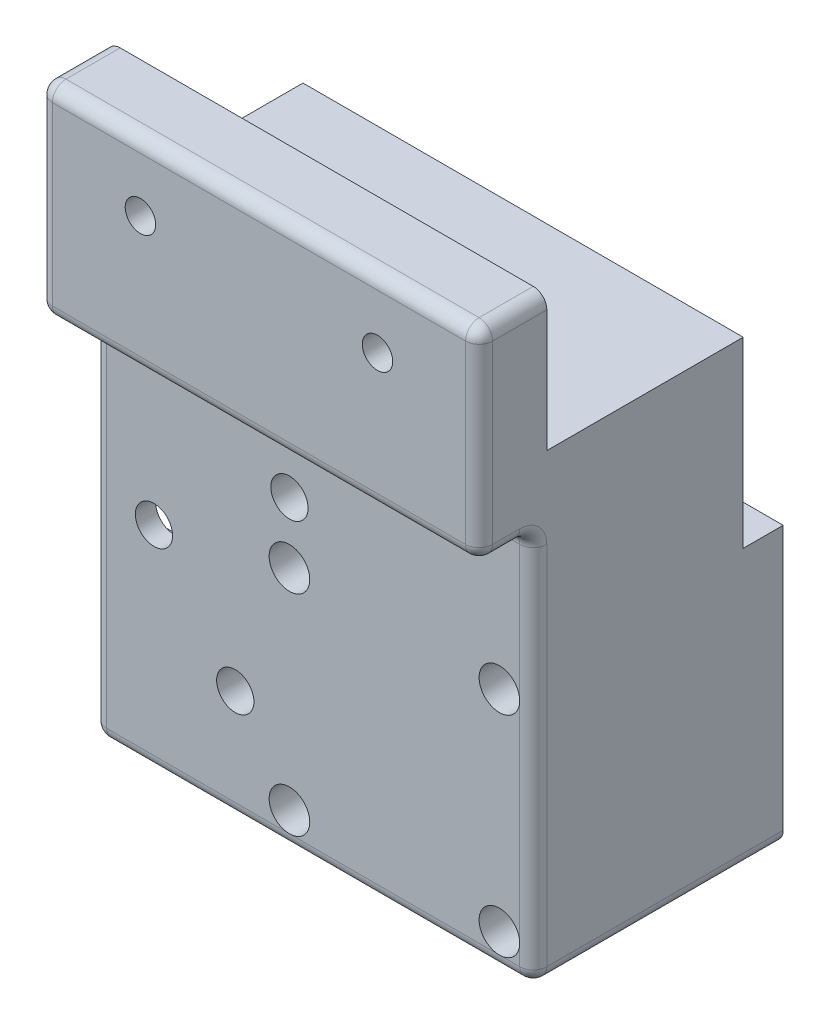
SolidWorks part; units mm, degrees
ref_plane "Front Plane" through (0, 0, 0) normal (0, 0, 1) x (1, 0, 0)
ref_plane "Top Plane" through (0, 0, 0) normal (0, 1, 0) x (1, 0, 0)
ref_plane "Right Plane" through (0, 0, 0) normal (1, 0, 0) x (0, 0, -1)
sketch "Sketch1" plane through (0, 0, 0) normal (0, 0, 1) x (1, 0, 0)
  line L1 (-44.5, 47.5) -> (20.5, 47.5)
  line L2 (-44.5, 47.5) -> (-44.5, -20.5)
  line L3 (-44.5, -20.5) -> (20.5, -20.5)
  line L4 (20.5, 47.5) -> (20.5, -20.5)
  circle A0 centre (0, 0) radius 12
  circle A1 centre (-15.5, 15.5) radius 1.75
  circle A2 centre (15.5, 15.5) radius 1.75
  circle A3 centre (15.5, -15.5) radius 1.75
  circle A4 centre (-15.5, -15.5) radius 1.75
  circle A6 centre (-15.5, 24.5) radius 2.75
  dimension "D1" = 24
  dimension "D2" = 31
  dimension "D3" = 31
  dimension "D4" = 31
  dimension "D5" = 31
  dimension "D6" = 15.5
  dimension "D7" = 15.5
  dimension "D8" = 0
  dimension "D9" = 3.5
  dimension "D10" = 3.5
  dimension "D11" = 3.5
  dimension "D12" = 3.5
  dimension "D13" = 23
  dimension "D14" = 29
  dimension "D16" = 5.5
  dimension "D21" = 47.5
  dimension "D22" = 44.5
  dimension "D19" = 65
  dimension "D20" = 68
extrude "Boss-Extrude1" add sketch "Sketch1" along normal blind 7
sketch "Sketch2" plane through (0, 0, 7) normal (0, 0, 1) x (1, 0, 0)
  line L0 (20.5, 47.5) -> (-44.5, 47.5) construction
  line L1 (-44.5, 47.5) -> (-44.5, -20.5) construction
  circle A0 centre (-15.5, 24.5) radius 2.75
  circle A6 centre (-35.5, 11) radius 2.75
  circle A8 centre (-23.5, -4.2471) radius 2.75
  circle A9 centre (-23.5, -4.2471) radius 7
  circle A10 centre (-15.5, 24.5) radius 7
  circle A11 centre (-35.5, 11) radius 4
  dimension "D1" = 14
  dimension "D2" = 5.5
  dimension "D3" = 5.5
  dimension "D4" = 8
  dimension "D6" = 14
  dimension "D5" = 23
  dimension "D8" = 29
  dimension "D9" = 36.5
  dimension "D10" = 9
  dimension "D11" = 51.7471
  dimension "D7" = 21
extrude "Boss-Extrude2" add sketch "Sketch2" along normal blind 2.65
sketch "Sketch3" plane through (20.5, 0, 0) normal (1, 0, 0) x (0, 0, -1)
  line L1 (-7, 47.5) -> (-29, 47.5)
  line L2 (-7, 47.5) -> (-7, 37.5)
  line L3 (-7, 37.5) -> (-29, 37.5)
  line L4 (-29, 47.5) -> (-29, 37.5)
  line L5 (-29, 37.5) -> (-39, 37.5)
  line L6 (-29, 37.5) -> (-29, 67.5)
  line L7 (-29, 67.5) -> (-39, 67.5)
  line L8 (-39, 37.5) -> (-39, 67.5)
  line M7 (-7, 47.5) -> (-7, -20.5)
  dimension "D1" = 22
  dimension "D2" = 10
  dimension "D3" = 20
  dimension "D4" = 10
extrude "Boss-Extrude3" add sketch "Sketch3" against normal through all contours L1 L4 L3 M7 | L8 L5 L4 L6 L7 region at (20.5, 42.5, 18) region at (20.5, 52.5, 34)
sketch "Sketch4" plane through (0, 0, 39) normal (0, 0, 1) x (1, 0, 0)
  line L0 (-44.5, 37.5) -> (20.5, 37.5) construction
  line L1 (-44.5, 67.5) -> (20.5, 67.5) construction
  line L2 (-44.5, 37.5) -> (-44.5, 67.5) construction
  line L3 (20.5, 37.5) -> (20.5, 67.5) construction
  circle A0 centre (-29.5, 57.5) radius 2.25
  circle A1 centre (5.5, 57.5) radius 2.25
  dimension "D1" = 4.5
  dimension "D2" = 20
  dimension "D3" = 10
  dimension "D4" = 15
  dimension "D5" = 10
  dimension "D6" = 15
  dimension "D7" = 4.5
extrude "Cut-Extrude1" cut sketch "Sketch4" against normal blind 10
sketch "Sketch5" plane through (0, 37.5, 0) normal (0, -1, 0) x (1, 0, 0)
  line L0 (-44.5, 7) -> (-44.5, 39) construction
  line L1 (-44.5, 39) -> (20.5, 39) construction
  line L2 (20.5, 7) -> (20.5, 39) construction
  circle A0 centre (-29.5, 19) radius 2.25
  circle A1 centre (5.5, 19) radius 2.25
  dimension "D1" = 15
  dimension "D2" = 20
  dimension "D3" = 20
  dimension "D4" = 15
  dimension "D5" = 4.5
  dimension "D6" = 4.5
extrude "Cut-Extrude2" cut sketch "Sketch5" against normal blind 10
sketch "Sketch7" plane through (0, 0, 0) normal (0, 0, -1) x (-1, 0, 0)
  line L1 (-20.5, -20.5) -> (20.5, -20.5)
  line L2 (-20.5, -20.5) -> (-20.5, 20.5)
  line L3 (-20.5, 20.5) -> (20.5, 20.5)
  line L4 (20.5, -20.5) -> (20.5, 20.5)
  circle A0 centre (0, 0) radius 12
  circle A1 centre (-15.5, 15.5) radius 1.75
  circle A2 centre (15.5, 15.5) radius 1.75
  circle A3 centre (15.5, -15.5) radius 1.75
  circle A4 centre (-15.5, -15.5) radius 1.75
  dimension "D2" = 5
  dimension "D3" = 5
  dimension "D4" = 5
  dimension "D1" = 5
extrude "Boss-Extrude5" add sketch "Sketch7" along normal blind 5.9
sketch "Sketch8" plane through (0, 0, 9.65) normal (0, 0, 1) x (1, 0, 0)
  circle A0 centre (-35.5, 11) radius 2.75
  circle A1 centre (-35.5, 11) radius 4
  dimension "D1" = 8
extrude "Boss-Extrude6" add sketch "Sketch8" along normal blind 7.95
sketch "Sketch10" plane through (0, 0, 7) normal (0, 0, 1) x (1, 0, 0)
  circle A0 centre (-35.5, 11) radius 2.75
  circle A1 centre (-23.5, -4.2471) radius 2.75
extrude "Cut-Extrude3" cut sketch "Sketch10" against normal blind 9.45
sketch "Sketch11" plane through (0, 0, 7) normal (0, 0, 1) x (1, 0, 0)
  line L1 (-44.5, 37.5) -> (20.5, 37.5)
  line L2 (-44.5, 37.5) -> (-44.5, -20.5)
  line L3 (-44.5, -20.5) -> (20.5, -20.5)
  line L4 (20.5, 37.5) -> (20.5, -20.5)
  circle A0 centre (-23.5, -4.2471) radius 10
  circle A1 centre (-15.5, 24.5) radius 10
  circle A2 centre (-15.5, 24.5) radius 2.75
  circle A3 centre (-23.5, -4.2471) radius 2.75
  circle A4 centre (0, 0) radius 7.25
  circle M1 centre (15.5, -15.5) radius 1.75
  circle M2 centre (-15.5, 15.5) radius 1.75
  circle M3 centre (0, 0) radius 12
  circle M4 centre (15.5, 15.5) radius 1.75
  circle M5 centre (-15.5, -15.5) radius 1.75
  circle M7 centre (-35.5, 11) radius 4
  line M9 (20.5, -20.5) -> (20.5, 37.5)
  line M10 (20.5, 37.5) -> (-44.5, 37.5)
  line M11 (-44.5, 37.5) -> (-44.5, -20.5)
  line M12 (-44.5, -20.5) -> (20.5, -20.5)
  dimension "D1" = 20
  dimension "D2" = 20
  dimension "D3" = 14.5
extrude "Boss-Extrude7" add sketch "Sketch11" along normal blind 10 contours A1 A0 M12 M9 M10 M11 M2 M4 M7 M5 M3 M1 | A4 M3 region at (-12.0095, 9.6819, 7) region at (-11.6606, 0, 7)
sketch "Sketch12" plane through (0, 0, 17) normal (0, 0, 1) x (1, 0, 0)
  line L1 (-11.6164, 26.7733) -> (3.0206, 1.7681)
  line L2 (-44.5, 37.5) -> (-44.5, -20.5) construction
  line L6 (-44.5, -20.5) -> (20.5, -20.5) construction
  line L7 (-44.5, 29) -> (-15.5, 29)
  line L8 (-44.5, 29) -> (-44.5, 32)
  line L9 (-44.5, 32) -> (-15.5, 32)
  line L13 (-9.0274, 28.2888) -> (5.6096, 3.2836)
  line L14 (-21.2843, 2.9181) -> (-1.034, -3.3438)
  line L17 (-22.1706, 0.052) -> (-1.9202, -6.2099)
  line L18 (-31, -4.2471) -> (-31, -20.5)
  line L20 (-31, -20.5) -> (-28, -20.5)
  line L21 (-28, -4.2471) -> (-28, -20.5)
  arc A5 (-21.2843, 2.9181) -> (-31, -4.2471) centre (-23.5, -4.2471) ccw
  arc A6 (-22.1706, 0.052) -> (-28, -4.2471) centre (-23.5, -4.2471) ccw
  arc A7 (-1.034, -3.3438) -> (3.0206, 1.7681) centre (0, 0) ccw
  arc A8 (-11.6164, 26.7733) -> (-15.5, 29) centre (-15.5, 24.5) ccw
  arc A9 (-9.0274, 28.2888) -> (-15.5, 32) centre (-15.5, 24.5) ccw
  arc A10 (-1.9202, -6.2099) -> (5.6096, 3.2836) centre (0, 0) ccw
  dimension "D4" = 3
  dimension "D5" = 3
  dimension "D6" = 3
  dimension "D7" = 3
extrude "Cut-Extrude4" cut sketch "Sketch12" against normal up to surface (7.35 mm away) up to face at (-16.5, -4.2471, 9.65)
sketch "Sketch13" plane through (0, 0, 17) normal (0, 0, 1) x (1, 0, 0)
  line L0 (-44.5, 29) -> (-44.5, -20.5) construction
  line L1 (-15.5, 34.5) -> (-44.5, 34.5)
  line L3 (-15.5, 14.5) -> (-44.5, 14.5)
  line L4 (-44.5, 34.5) -> (-44.5, 14.5)
  line L11 (-23.5, 5.7529) -> (-44.5, 5.7529)
  line L13 (-23.5, -14.2471) -> (-44.5, -14.2471)
  line L14 (-44.5, 5.7529) -> (-44.5, -14.2471)
  arc A0 (-15.5, 14.5) -> (-15.5, 34.5) centre (-15.5, 24.5) ccw
  circle A1 centre (-15.5, 24.5) radius 7
  circle A2 centre (-23.5, -4.2471) radius 7
  arc A4 (-23.5, -14.2471) -> (-23.5, 5.7529) centre (-23.5, -4.2471) ccw
extrude "Cut-Extrude5" cut sketch "Sketch13" against normal up to surface (10 mm away) up to face at (-15.5, 25.875, 7)
sketch "Sketch14" plane through (0, 0, 17) normal (0, 0, 1) x (1, 0, 0)
  circle A0 centre (15.5, 15.5) radius 3
  circle A1 centre (15.5, -15.5) radius 3
  circle A2 centre (-15.5, -15.5) radius 3
  circle A3 centre (-15.5, 15.5) radius 3
  dimension "D1" = 6
extrude "Cut-Extrude6" cut sketch "Sketch14" against normal blind 17
sketch "Sketch15" plane through (0, 0, 17) normal (0, 0, 1) x (1, 0, 0)
  line L0 (-44.5, 37.5) -> (20.5, 37.5)
  line L1 (20.5, 37.5) -> (20.5, -20.5)
  line L8 (-26.9872, 5.7529) -> (-23.5, 5.7529)
  line L9 (-26.1325, 14.5) -> (-18.3284, 14.5)
  line L10 (-15.5, 34.5) -> (-44.5, 34.5)
  line L11 (-44.5, 34.5) -> (-44.5, 37.5)
  line L12 (-14.9652, 0.9641) -> (-7.0998, -1.4681)
  line L13 (-4.9882, -5.2612) -> (-13.6389, -2.5862)
  line L14 (3.9873, 6.055) -> (-5.686, 22.5805)
  line L15 (-7.1051, 19.0663) -> (-0.1869, 7.2476)
  line L18 (-28, -20.5) -> (-28, -14.2471)
  line L19 (-28, -14.2471) -> (-23.5, -14.2471)
  line L21 (-44.5, -20.5) -> (-31, -20.5)
  line L22 (-44.5, -20.5) -> (-44.5, -14.2471)
  line L23 (-44.5, -14.2471) -> (-31, -14.2471)
  line L24 (-31, -20.5) -> (-31, -14.2471)
  line L25 (-28, -20.5) -> (20.5, -20.5)
  arc A0 (-12.5519, 14.9444) -> (-7.1051, 19.0663) centre (-15.5, 24.5) ccw
  arc A1 (-18.3284, 14.5) -> (-12.5519, 14.9444) centre (-15.5, 15.5) ccw
  arc A4 (-4.9882, -5.2612) -> (3.9873, 6.055) centre (0, 0) ccw
  circle A5 centre (15.5, 15.5) radius 3
  circle A6 centre (15.5, -15.5) radius 3
  arc A8 (-0.1869, 7.2476) -> (-7.0998, -1.4681) centre (0, 0) ccw
  arc A12 (-5.686, 22.5805) -> (-15.5, 34.5) centre (-15.5, 24.5) ccw
  circle A15 centre (-15.5, -15.5) radius 3
  arc A18 (-14.9652, 0.9641) -> (-23.5, 5.7529) centre (-23.5, -4.2471) ccw
  arc A19 (-26.9872, 5.7529) -> (-26.1325, 14.5) centre (-35.5, 11) ccw
  arc A20 (-23.5, -14.2471) -> (-13.6389, -2.5862) centre (-23.5, -4.2471) ccw
extrude "Boss-Extrude9" add sketch "Sketch15" along normal blind 3.5
sketch "Sketch16" plane through (0, 0, 20.5) normal (0, 0, 1) x (1, 0, 0)
  line L1 (-44.5, 37.5) -> (20.5, 37.5)
  line L2 (-44.5, 37.5) -> (-44.5, -20.5)
  line L3 (-44.5, -20.5) -> (20.5, -20.5)
  line L4 (20.5, 37.5) -> (20.5, -20.5)
  arc A0 (-44.5, 6.6411) -> (-44.5, 15.3589) centre (-35.5, 11) ccw
  circle A1 centre (-15.5, 15.5) radius 3
  circle A2 centre (15.5, 15.5) radius 3
  circle A3 centre (15.5, -15.5) radius 3
  circle A4 centre (-15.5, -15.5) radius 3
  circle M1 centre (15.5, -15.5) radius 3
  line M2 (-44.5, 37.5) -> (-44.5, 34.5)
  line M3 (-44.5, 34.5) -> (-15.5, 34.5)
  arc M4 (-15.5, 34.5) -> (-5.686, 22.5805) centre (-15.5, 24.5) cw
  line M5 (-5.686, 22.5805) -> (3.9873, 6.055)
  arc M6 (3.9873, 6.055) -> (-4.9882, -5.2612) centre (0, 0) cw
  line M7 (-4.9882, -5.2612) -> (-13.6389, -2.5862)
  arc M8 (-13.6389, -2.5862) -> (-23.5, -14.2471) centre (-23.5, -4.2471) cw
  line M9 (-23.5, -14.2471) -> (-28, -14.2471)
  line M10 (-28, -14.2471) -> (-28, -20.5)
  line M11 (-28, -20.5) -> (20.5, -20.5)
  line M12 (20.5, -20.5) -> (20.5, 37.5)
  line M13 (20.5, 37.5) -> (7.1771, 37.5)
  line M14 (7.1771, 37.5) -> (3.8229, 37.5)
  line M15 (3.8229, 37.5) -> (-27.8229, 37.5)
  line M16 (-27.8229, 37.5) -> (-31.1771, 37.5)
  line M17 (-31.1771, 37.5) -> (-44.5, 37.5)
  circle M18 centre (15.5, 15.5) radius 3
  circle M19 centre (-15.5, -15.5) radius 3
extrude "Boss-Extrude10" add sketch "Sketch16" along normal blind 7.5 contours A0 L2 L3 A1 M10 M9 M8 M7 M6 M5 M4 M3 | M17 M2 M3 M4 M5 M6 M7 M8 M9 M10 M11 M12 M13 M14 M15 M16 M19 M18 M1 region at (2.7798, 8.7673, 20.5) region at (-21.9314, 8.3685, 20.5)
sketch "Sketch17" plane through (0, 0, 28) normal (0, 0, 1) x (1, 0, 0)
  line L1 (-44.5, 37.5) -> (20.5, 37.5)
  line L2 (-44.5, 37.5) -> (-44.5, -20.5)
  line L3 (-44.5, -20.5) -> (20.5, -20.5)
  line L4 (20.5, 37.5) -> (20.5, -20.5)
  circle A0 centre (-15.5, 15.5) radius 3
  circle A1 centre (15.5, 15.5) radius 3
  circle A2 centre (15.5, -15.5) radius 3
  circle A3 centre (-15.5, -15.5) radius 3
extrude "Boss-Extrude11" add sketch "Sketch17" along normal blind 3
sketch "Sketch18" plane through (0, 47.5, 0) normal (0, 1, 0) x (1, 0, 0)
  circle A0 centre (-29.5, -19) radius 2.25
  circle A1 centre (5.5, -19) radius 2.25
extrude "Cut-Extrude7" cut sketch "Sketch18" against normal through all
sketch "Sketch19" plane through (0, -20.5, 0) normal (0, -1, 0) x (1, 0, 0)
  circle A0 centre (-29.5, 19) radius 3.75
  circle A1 centre (5.5, 19) radius 3.75
  dimension "D1" = 7.5
  dimension "D2" = 7.5
extrude "Cut-Extrude8" cut sketch "Sketch19" against normal blind 58
fillet "Fillet2" radius 2 14 edges at (20.5, 37.5, 35) (-44.5, 37.5, 35) (-44.5, 67.5, 34) (20.5, 67.5, 34) (-12, 67.5, 39) (20.5, 52.5, 39) (-44.5, 52.5, 39) (-12, 37.5, 31) (-12, 37.5, 39) (20.5, 8.5, 31) (20.5, -20.5, 12.55) (-12, -20.5, 31) (-44.5, -20.5, 15.5) (-44.5, 8.5, 31)
sketch "Sketch20" plane through (0, 0, 0) normal (0, 0, -1) x (-1, 0, 0)
  line L0 (20.5, 20.5) -> (-20.5, 20.5) construction
  line L1 (13.0463, 28.75) -> (10.5925, 24.5)
  line L2 (10.5925, 24.5) -> (13.0463, 20.25)
  line L3 (13.0463, 20.25) -> (17.9537, 20.25)
  line L4 (17.9537, 20.25) -> (20.4075, 24.5)
  line L5 (20.4075, 24.5) -> (17.9537, 28.75)
  line L6 (17.9537, 28.75) -> (13.0463, 28.75)
  line L7 (39.75, 13.4537) -> (35.5, 15.9075)
  line L8 (35.5, 15.9075) -> (31.25, 13.4537)
  line L9 (31.25, 13.4537) -> (31.25, 8.5463)
  line L10 (31.25, 8.5463) -> (35.5, 6.0925)
  line L11 (35.5, 6.0925) -> (39.75, 8.5463)
  line L12 (39.75, 8.5463) -> (39.75, 13.4537)
  line L13 (23.5, 0.6603) -> (19.25, -1.7934)
  line L14 (19.25, -1.7934) -> (19.25, -6.7009)
  line L15 (19.25, -6.7009) -> (23.5, -9.1546)
  line L16 (23.5, -9.1546) -> (27.75, -6.7009)
  line L17 (27.75, -6.7009) -> (27.75, -1.7934)
  line L18 (27.75, -1.7934) -> (23.5, 0.6603)
  line L19 (20.5, -20.5) -> (20.5, 20.5) construction
  line L20 (20.5, -20.5) -> (20.5, 20.5) construction
  circle A0 centre (15.5, 24.5) radius 4.25 construction
  circle A1 centre (35.5, 11) radius 4.25 construction
  circle A2 centre (23.5, -4.2471) radius 4.25 construction
  point P33 (33.375, 14.6806)
  dimension "D1" = 8.5
extrude "Cut-Extrude9" cut sketch "Sketch20" against normal blind 5.5
sketch "Sketch21" plane through (0, 0, 0) normal (0, 0, -1) x (-1, 0, 0)
  line L1 (17.9537, 28.75) -> (13.0463, 28.75)
  line L2 (13.0463, 28.75) -> (10.5925, 24.5)
  line L3 (10.5925, 24.5) -> (13.0463, 20.25)
  line L4 (13.0463, 20.25) -> (17.9537, 20.25)
  line L5 (17.9537, 20.25) -> (20.4075, 24.5)
  line L6 (20.4075, 24.5) -> (17.9537, 28.75)
  line L7 (27.75, -1.7934) -> (23.5, 0.6603)
  line L8 (23.5, 0.6603) -> (19.25, -1.7934)
  line L9 (19.25, -1.7934) -> (19.25, -6.7009)
  line L10 (19.25, -6.7009) -> (23.5, -9.1546)
  line L11 (23.5, -9.1546) -> (27.75, -6.7009)
  line L12 (27.75, -6.7009) -> (27.75, -1.7934)
  circle A0 centre (15.5, 24.5) radius 4.25 construction
  circle A1 centre (23.5, -4.2471) radius 4.25 construction
extrude "Cut-Extrude10" cut sketch "Sketch21" along normal blind 29.5
sketch "Sketch22" plane through (0, 0, 5.5) normal (0, 0, -1) x (-1, 0, 0)
  circle A0 centre (23.5, -4.2471) radius 2.75
  circle A1 centre (35.5, 11) radius 2.75
  circle A2 centre (15.5, 24.5) radius 2.75
extrude "Cut-Extrude11" cut sketch "Sketch22" against normal blind 26
sketch "Sketch23" plane through (0, 0, 20.5) normal (0, 0, -1) x (-1, 0, 0)
  line L0 (44.5, 34.5) -> (44.5, 15.3589) construction
  line L1 (35.5, 1) -> (44.5, 1)
  line L2 (35.5, 1) -> (35.5, 21)
  line L3 (35.5, 21) -> (44.5, 21)
  line L4 (44.5, 1) -> (44.5, 21)
  arc A0 (32.9369, 1.334) -> (44.5, 6.6411) centre (35.5, 11) ccw construction
extrude "Cut-Extrude12" cut sketch "Sketch23" against normal up to surface (7.5 mm away) up to face at (-32.75, 11, 28)
sketch "Sketch25" plane through (0, -20.5, 0) normal (0, -1, 0) x (1, 0, 0)
  line L0 (18.5, 29) -> (-42.5, 29) construction
  line L1 (-31, 9.65) -> (-28, 9.65)
  line L2 (-31, 9.65) -> (-31, 29)
  line L3 (-31, 29) -> (-28, 29)
  line L4 (-28, 9.65) -> (-28, 29)
extrude "Cut-Extrude18" cut sketch "Sketch25" against normal blind 29
